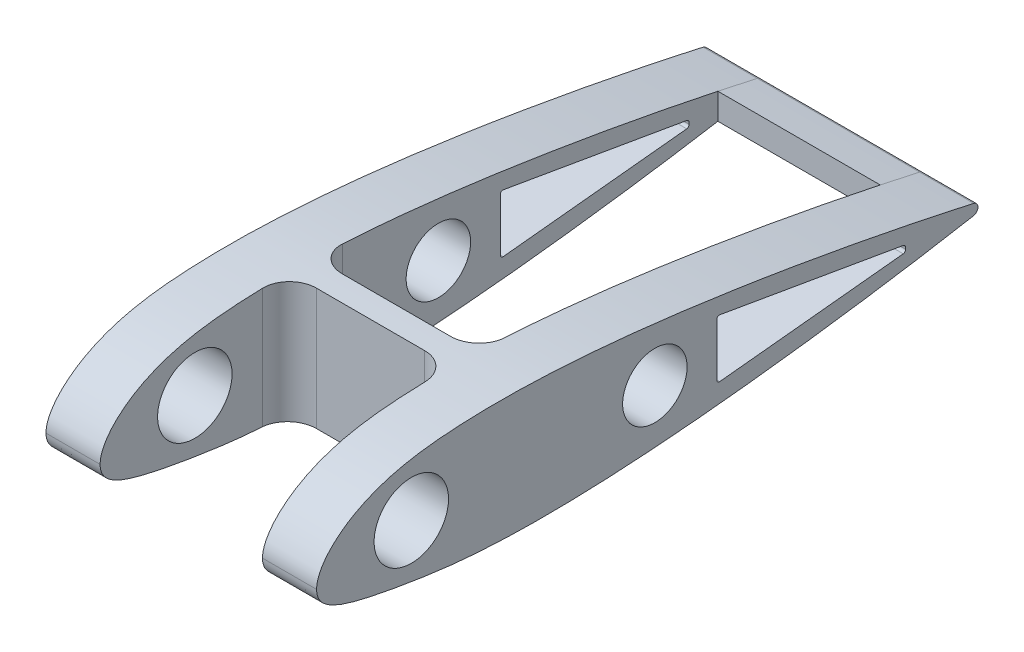
SolidWorks part; units mm, degrees
ref_plane "Front Plane" through (0, 0, 0) normal (0, 0, 1) x (1, 0, 0)
ref_plane "Top Plane" through (0, 0, 0) normal (0, 1, 0) x (1, 0, 0)
ref_plane "Right Plane" through (0, 0, 0) normal (1, 0, 0) x (0, 0, -1)
sketch "Sketch1" plane through (0, 0, 0) normal (1, 0, 0) x (0, 0, -1)
  line L0 (0, 0) -> (126.1538, 0) construction
  line L1 (37.5, 13.186) -> (37.5, -14.32)
  line L2 (87.5, 7.698) -> (87.5, -11.041)
  line L3 (34.966, 0) -> (34.966, 13.2248)
  line L4 (34.966, 0) -> (34.966, -9.2469)
  line L5 (39.739, -9.3563) -> (39.739, 13.1232)
  line L6 (73.937, 6.1934) -> (73.937, -3.4953)
  line L7 (74.4883, -3.9926) -> (108.3873, -0.4988)
  line L8 (108.836, 0.3374) -> (108.836, -0.0014)
  line L9 (108.4211, 0.8301) -> (74.5221, 6.6861)
  line L10 (112.5, 2.9996) -> (112.5, -2.4379) construction
  line L11 (97.8987, 6.564) -> (108.4211, 4.3429)
  line L12 (112.5, 2.9996) -> (112.5753, 3.466) construction
  line L13 (97.8987, 6.564) -> (127.2519, 0.3679)
  circle A0 centre (17.5, 2.293) radius 6.875
  circle A1 centre (62.5, 1.381) radius 5.956
  arc A2 (73.937, -3.4953) -> (74.4883, -3.9926) centre (74.437, -3.4953) ccw
  arc A3 (73.937, 6.1934) -> (74.5221, 6.6861) centre (74.437, 6.1934) cw
  arc A4 (108.836, 0.3374) -> (108.4211, 0.8301) centre (108.336, 0.3374) ccw
  arc A5 (108.3873, -0.4988) -> (108.836, -0.0014) centre (108.336, -0.0014) ccw
  arc A6 (121.4237, 1.0553) -> (121.3823, -0.9043) centre (121.2041, 0.0797) cw
  spline S0 degree 3 number of poles 123 (0, 0) -> (121.4237, 1.0553)
  spline S1 degree 3 number of poles 116 (0, 0) -> (121.3823, -0.9043)
  point P238 (112.5753, 3.466)
  point P268 (112.5, 2.9996)
  dimension "D1" = 0.5
  dimension "D2" = 1
sketch "Sketch2" plane through (0, 0, 0) normal (1, 0, 0) x (0, 0, -1)
  spline S0 degree 3 number of poles 116 (0, 0) -> (121.3823, -0.9043) construction
  spline S1 degree 3 number of poles 123 (0, 0) -> (121.4237, 1.0553) construction
  spline S2 degree 3 number of poles 116 (0, 0) -> (121.3823, -0.9043)
  spline S3 degree 3 number of poles 123 (0, 0) -> (121.4237, 1.0553)
ref_plane "Plane1" through (50, 0, 0) normal (1, 0, 0) x (0, 0, -1)
sketch "Sketch3" plane through (50, 0, 0) normal (1, 0, 0) x (0, 0, -1)
  arc A0 (121.3823, -0.9043) -> (121.4237, 1.0553) centre (121.2041, 0.0797) ccw construction
  arc A1 (121.3823, -0.9043) -> (121.4237, 1.0553) centre (121.2041, 0.0797) ccw
  spline S0 degree 3 number of poles 116 (0, 0) -> (121.3823, -0.9043) construction
  spline S1 degree 3 number of poles 123 (0, 0) -> (121.4237, 1.0553) construction
  spline S2 degree 3 number of poles 116 (0, 0) -> (121.3823, -0.9043)
  spline S3 degree 3 number of poles 123 (0, 0) -> (121.4237, 1.0553)
extrude "Boss-Extrude1" add sketch "Sketch3" against normal blind 10
sketch "Sketch4" plane through (0, 0, 0) normal (1, 0, 0) x (0, 0, -1)
  arc A0 (121.3823, -0.9043) -> (121.4237, 1.0553) centre (121.2041, 0.0797) ccw construction
  arc A1 (121.3823, -0.9043) -> (121.4237, 1.0553) centre (121.2041, 0.0797) ccw
  spline S0 degree 3 number of poles 116 (0, 0) -> (121.3823, -0.9043) construction
  spline S1 degree 3 number of poles 123 (0, 0) -> (121.4237, 1.0553) construction
  spline S2 degree 3 number of poles 116 (0, 0) -> (121.3823, -0.9043)
  spline S3 degree 3 number of poles 123 (0, 0) -> (121.4237, 1.0553)
extrude "Boss-Extrude2" add sketch "Sketch4" along normal blind 10 separate body
ref_plane "Plane2" through (0, 26.0678, -5.5026) normal (0, -0.9784, 0.2065) x (0, -0.2065, -0.9784)
sketch "Sketch5" plane through (0, 26.0678, -5.5026) normal (0, -0.9784, 0.2065) x (0, -0.2065, -0.9784)
  line L0 (101.9322, 0) -> (116.9322, 0)
  line L1 (101.9322, 0) -> (101.9322, 3.6798)
  line L2 (101.9322, 3.6798) -> (116.9322, 3.6798)
  line L3 (116.9322, 3.6798) -> (116.9322, 0)
  point P5 (109.4322, 0)
sketch "Sketch7" plane through (0, 0, 0) normal (-1, 0, 0) x (0, 0, 1)
  line L0 (-34.966, 0) -> (-34.966, 13.2248) construction
  line L1 (-34.966, 0) -> (-34.966, -9.2469) construction
  line L2 (-39.739, -9.3563) -> (-39.739, 13.1232) construction
  line L3 (-34.966, 0) -> (-34.966, 13.2248)
  line L4 (-34.966, 0) -> (-34.966, -9.2469)
  line L5 (-39.739, -9.3563) -> (-39.739, 13.1232)
  spline S0 degree 3 number of poles 123 (0, 0) -> (-121.4237, 1.0553) construction
  spline S1 degree 3 number of poles 116 (0, 0) -> (-121.3823, -0.9043) construction
  spline S2 degree 3 poles (-34.966, 13.2248) (-35.5314, 13.2204) (-36.4408, 13.2084) (-37.6961, 13.1829) (-38.5614, 13.1605) (-39.243, 13.1397) (-39.5787, 13.1287) (-39.739, 13.1232) knots 0.303259 0.303259 0.303259 0.303259 0.316064 0.323856 0.331694 0.335667 0.3393 0.3393 0.3393 0.3393
  spline S3 degree 3 poles (-34.966, -9.2469) (-35.022, -9.249) (-35.2463, -9.2571) (-35.7265, -9.2732) (-36.5798, -9.2986) (-37.4378, -9.3205) (-38.3883, -9.3385) (-39.07, -9.3492) (-39.5787, -9.3547) (-39.739, -9.3563) knots 0.291805 0.291805 0.291805 0.291805 0.293101 0.296999 0.302921 0.312855 0.316859 0.324921 0.328631 0.328631 0.328631 0.328631
extrude "Boss-Extrude5" add sketch "Sketch7" against normal up to surface (50 mm away) up to face at (50, 0.3713, -81.2092)
extrude "Cut-Extrude2" cut sketch "Sketch1" against normal through all and the other way through all contours A0 | A1 | L9 A3 L6 A2 L7 A5 L8 A4
sketch "Sketch10" plane through (0, 0, 0) normal (-1, 0, 0) x (0, 0, 1)
  line L0 (-119.9136, 1.917) -> (-119.9136, -1.1681)
  arc A3 (-121.4237, 1.0553) -> (-121.3823, -0.9043) centre (-121.2041, 0.0797) ccw
  arc A6 (-121.4237, 1.0553) -> (-121.3823, -0.9043) centre (-121.2041, 0.0797) ccw
  spline S2 degree 3 number of poles 116 (-121.3823, -0.9043) -> (0, 0)
  spline S3 degree 3 number of poles 123 (0, 0) -> (-121.4237, 1.0553)
  spline S4 degree 3 poles (-121.3823, -0.9043) (-120.8929, -0.9929) (-120.4033, -1.0809) (-119.9136, -1.1681) knots 0 0 0 0 0.01151 0.01151 0.01151 0.01151
  spline S5 degree 3 number of poles 123 (0, 0) -> (-121.4237, 1.0553)
  dimension "D1" = 0
combine bodies "Combine1" operation type add bodies to combine 106 109 105
fillet "Fillet2" radius 5 4 edges at (40, 1.8835, -39.739) (40, 1.9889, -34.966) (10, 1.9889, -34.966) (10, 1.8835, -39.739)
sketch "Sketch12" plane through (10, 0, 0) normal (1, 0, 0) x (0, 0, -1)
  line L0 (114.1373, -2.1658) -> (114.1373, 2.6462)
  line L1 (44.739, 12.8935) -> (44.739, -9.3481)
  line L2 (44.739, 12.8935) -> (44.739, -9.3481)
  arc A1 (121.3823, -0.9043) -> (121.4237, 1.0553) centre (121.2041, 0.0797) ccw
  arc A2 (121.3823, -0.9043) -> (121.4237, 1.0553) centre (121.2041, 0.0797) ccw
  spline S2 degree 3 poles (979.8592, 2866.1374) (311.1923, -70.2195) (218.4213, -20.4819) (119.0757, 1.5796) (117.7267, 1.8761) (115.6605, 2.3236) (112.1447, 3.0709) (108.1601, 3.8872) (104.2976, 4.6492) (101.3525, 5.2177) (98.3381, 5.7832) (95.6501, 6.2769) (93.3151, 6.6938) (91.7457, 6.9714) (90.56, 7.1762) (89.1675, 7.4168) (87.5721, 7.6872) (85.9712, 7.9535) (84.7662, 8.1516) (82.9529, 8.4456) (81.3386, 8.703) (79.9241, 8.9222) (79.317, 9.0149) (78.5075, 9.1393) (77.0688, 9.3569) (75.247, 9.6266) (73.4257, 9.8881) (72.0325, 10.0834) (70.8215, 10.2504) (69.6122, 10.4145) (68.0042, 10.6276) (66.3998, 10.8332) (64.2041, 11.1067) (62.0219, 11.3645) (60.0415, 11.5883) (58.6641, 11.7347) (57.6865, 11.8375) (56.325, 11.9763) (54.7777, 12.1258) (53.0481, 12.2854) (51.457, 12.4219) (50.1301, 12.5272) (49.0015, 12.6145) (47.7593, 12.7039) (-98.254, 22.4222) (-251.9713, -90.66) (-269.1605, -2951.778) knots -2.276292 -2.276292 -2.276292 -2.276292 0.007092 0.018963 0.028431 0.038372 0.066843 0.109832 0.130486 0.156003 0.177763 0.199944 0.217897 0.23148 0.236039 0.245147 0.263485 0.272684 0.281902 0.291141 0.314286 0.318923 0.323559 0.328195 0.337472 0.356511 0.369903 0.379143 0.388371 0.397589 0.40678 0.425108 0.434221 0.456891 0.474871 0.479358 0.488262 0.497132 0.510352 0.523467 0.536469 0.546518 0.553613 0.562105 0.574725 3.86773 3.86773 3.86773 3.86773 only from (121.4237, 1.0553) to (44.739, 12.8935)
  spline S3 degree 3 poles (-193.9547, 2969.916) (-182.8486, 67.4486) (-67.7316, -11.3827) (46.5531, -9.3183) (47.945, -9.2877) (49.3483, -9.2458) (51.0491, -9.1884) (53.2459, -9.1001) (55.5544, -8.9851) (57.6896, -8.8639) (59.2546, -8.7687) (60.8292, -8.6644) (62.4126, -8.5528) (64.4025, -8.4055) (66.6019, -8.229) (68.8091, -8.039) (70.8223, -7.8569) (73.0447, -7.6481) (75.2693, -7.4262) (77.9002, -7.1517) (80.5293, -6.8663) (82.9528, -6.5882) (85.7664, -6.2551) (88.5619, -5.9117) (91.7385, -5.5043) (94.4827, -5.1379) (96.4275, -4.8697) (98.3497, -4.6031) (99.6781, -4.4138) (101.3714, -4.1664) (103.2143, -3.8962) (105.2152, -3.5935) (107.3535, -3.2639) (109.0891, -2.9905) (110.7854, -2.7188) (112.7323, -2.4009) (114.6196, -2.0861) (116.5823, -1.7517) (118.0017, -1.5062) (263.2383, 24.0811) (398.514, 102.5406) (-1.4095, 2978.3227) knots -2.253072 -2.253072 -2.253072 -2.253072 0.370516 0.381162 0.391901 0.402732 0.413649 0.43128 0.453607 0.467134 0.480766 0.489888 0.503651 0.517496 0.53606 0.55471 0.568759 0.582836 0.606361 0.620491 0.644047 0.667556 0.676938 0.709609 0.732729 0.751047 0.773672 0.778158 0.795952 0.804722 0.817757 0.839053 0.851548 0.867821 0.87971 0.891301 0.91347 0.923986 0.937372 0.946802 4.336519 4.336519 4.336519 4.336519 only from (44.739, -9.3481) to (121.3823, -0.9043)
  spline S4 degree 3 poles (121.4237, 1.0553) (121.1182, 1.1241) (120.3012, 1.3075) (119.0757, 1.5796) (117.7267, 1.8761) (116.1153, 2.2251) (114.9118, 2.4822) (114.1373, 2.6462) knots 0 0 0 0 0.007092 0.018963 0.028431 0.038372 0.056302 0.056302 0.056302 0.056302
  spline S5 degree 3 poles (114.1373, -2.1658) (114.4636, -2.1111) (115.238, -1.9807) (116.5823, -1.7517) (118.0017, -1.5062) (119.6425, -1.2171) (120.7131, -1.0255) (121.3823, -0.9043) knots 0.905815 0.905815 0.905815 0.905815 0.91347 0.923986 0.937372 0.946802 0.962539 0.962539 0.962539 0.962539
  dimension "D1" = 0
extrude "Boss-Extrude6" add sketch "Sketch12" along normal up to surface (30 mm away) contours S4 L0 S5 A2 up to face at (40, -1.6154, -83.2764)
